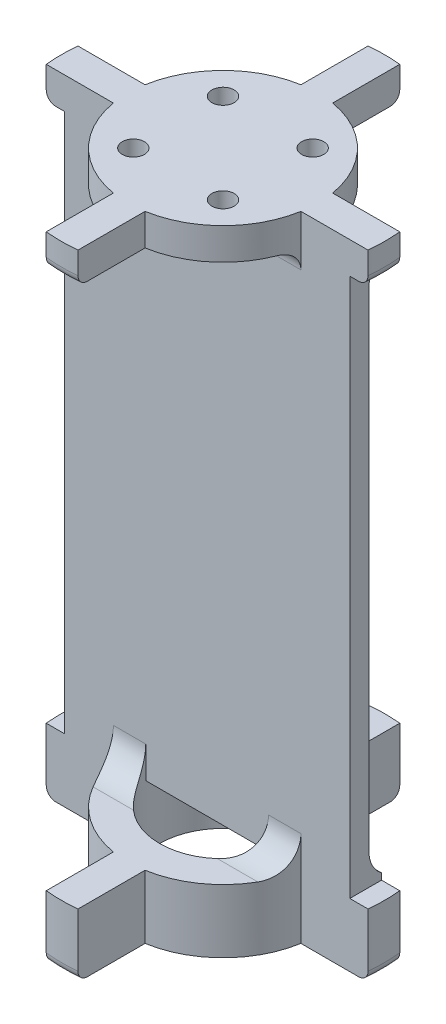
SolidWorks part; units mm, degrees
ref_plane "Front Plane" through (0, 0, 0) normal (0, 0, 1) x (1, 0, 0)
ref_plane "Top Plane" through (0, 0, 0) normal (0, 1, 0) x (1, 0, 0)
ref_plane "Right Plane" through (0, 0, 0) normal (1, 0, 0) x (0, 0, -1)
sketch "Sketch1" plane through (0, 0, 0) normal (0, 1, 0) x (1, 0, 0)
  line L0 (0, 33.2588) -> (0, -37.8737) construction
  line L1 (-37.1311, 0) -> (43.4964, 0) construction
  line L2 (-25.3772, 2.5) -> (-14.7902, 2.5)
  line L3 (-25.3772, -2.5) -> (-14.7902, -2.5)
  line L4 (2.5, 25.3772) -> (2.5, 14.7902)
  line L5 (-2.5, 25.3772) -> (-2.5, 14.7902)
  line L6 (25.3772, -2.5) -> (14.7902, -2.5)
  line L7 (25.3772, 2.5) -> (14.7902, 2.5)
  line L8 (-2.5, -25.3772) -> (-2.5, -14.7902)
  line L9 (2.5, -25.3772) -> (2.5, -14.7902)
  arc A0 (-25.3772, 2.5) -> (-25.3772, -2.5) centre (0, 0) ccw construction
  arc A1 (2.5, -14.7902) -> (14.7902, -2.5) centre (0, 0) ccw
  arc A2 (-25.3772, 2.5) -> (-25.3772, -2.5) centre (0, 0) ccw
  circle A3 centre (0, 0) radius 10
  arc A4 (2.5, 25.3772) -> (-2.5, 25.3772) centre (0, 0) ccw construction
  arc A5 (2.5, 25.3772) -> (-2.5, 25.3772) centre (0, 0) ccw
  arc A6 (25.3772, -2.5) -> (25.3772, 2.5) centre (0, 0) ccw construction
  arc A7 (25.3772, -2.5) -> (25.3772, 2.5) centre (0, 0) ccw
  arc A8 (-2.5, -25.3772) -> (2.5, -25.3772) centre (0, 0) ccw construction
  arc A9 (-2.5, -25.3772) -> (2.5, -25.3772) centre (0, 0) ccw
  arc A10 (-14.7902, -2.5) -> (-2.5, -14.7902) centre (0, 0) ccw
  arc A11 (-2.5, 14.7902) -> (-14.7902, 2.5) centre (0, 0) ccw
  arc A12 (14.7902, 2.5) -> (2.5, 14.7902) centre (0, 0) ccw
  point P29 (0, 0)
  dimension "D1" = 51
  dimension "D3" = 20
  dimension "D4" = 30
  dimension "D2" = 5
  dimension "D5" = 4
extrude "Boss-Extrude1" add sketch "Sketch1" along normal blind 10
sketch "Sketch3" plane through (0, 10, 0) normal (0, 1, 0) x (1, 0, 0)
  line L0 (-31.8047, -1) -> (31.2293, -1) construction
  line L2 (-22.5, -2.5) -> (22.5, -2.5)
  line L3 (-22.5, -2.5) -> (-22.5, 0.5)
  line L4 (-22.5, 0.5) -> (22.5, 0.5)
  line L5 (22.5, -2.5) -> (22.5, 0.5)
  line L6 (-22.5, -2.5) -> (22.5, 0.5) construction
  line L7 (-22.5, 0.5) -> (22.5, -2.5) construction
  circle A0 centre (0, 0) radius 25.5 construction
  point P5 (0, -1)
  dimension "D2" = 3
  dimension "D1" = 1
  dimension "D3" = 45
extrude "Boss-Extrude2" add sketch "Sketch3" along normal blind 85
fillet "Fillet1" radius 5 4 edges at (12.2363, 10, 2.5) (-12.2363, 10, 2.5) (16.2437, 10, -0.5) (-16.2437, 10, -0.5)
sketch "Sketch4" plane through (0, 95, 0) normal (0, 1, 0) x (1, 0, 0)
  line L0 (-27.7787, 0) -> (-15, 0) construction
  line L1 (0, 26.9654) -> (0, 15) construction
  line L2 (-25.3772, 2.5) -> (-14.7902, 2.5)
  line L3 (-25.3772, -2.5) -> (-14.7902, -2.5)
  line L4 (2.5, 25.3772) -> (2.5, 14.7902)
  line L5 (-2.5, 25.3772) -> (-2.5, 14.7902)
  line L6 (25.3772, -2.5) -> (14.7902, -2.5)
  line L7 (25.3772, 2.5) -> (14.7902, 2.5)
  line L8 (-2.5, -25.3772) -> (-2.5, -14.7902)
  line L9 (2.5, -25.3772) -> (2.5, -14.7902)
  line L10 (15, 0) -> (29.4054, 0) construction
  line L11 (0, 0) -> (0, -26.9341) construction
  line L12 (0, 0) -> (-20.6776, 20.6776) construction
  arc A0 (-25.3772, 2.5) -> (-25.3772, -2.5) centre (0, 0) ccw
  arc A1 (2.5, -14.7902) -> (14.7902, -2.5) centre (0, 0) ccw
  arc A2 (2.5, 25.3772) -> (-2.5, 25.3772) centre (0, 0) ccw
  arc A3 (25.3772, -2.5) -> (25.3772, 2.5) centre (0, 0) ccw
  arc A4 (-2.5, -25.3772) -> (2.5, -25.3772) centre (0, 0) ccw
  arc A5 (-14.7902, -2.5) -> (-2.5, -14.7902) centre (0, 0) ccw
  arc A6 (-2.5, 14.7902) -> (-14.7902, 2.5) centre (0, 0) ccw
  arc A7 (14.7902, 2.5) -> (2.5, 14.7902) centre (0, 0) ccw
  circle A8 centre (-7.0711, 7.0711) radius 1.75
  circle A9 centre (7.0711, 7.0711) radius 1.75
  circle A10 centre (7.0711, -7.0711) radius 1.75
  circle A11 centre (-7.0711, -7.0711) radius 1.75
  point P29 (0, 0)
  point P40 (0, 0)
  dimension "D2" = 3.5
  dimension "D3" = 10
  dimension "D1" = 4
  dimension "D4" = 4
extrude "Boss-Extrude3" add sketch "Sketch4" along normal blind 5
fillet "Fillet2" radius 3 2 edges at (0, 95, 2.5) (0, 95, -0.5)
fillet "Fillet3" radius 1.5 8 edges at (25.5, 95, 0) (0, 95, 25.5) (-25.5, 95, 0) (0, 95, -25.5) (25.5, 0, 0) (0, 0, 25.5) (-25.5, 0, 0) (0, 0, -25.5)
